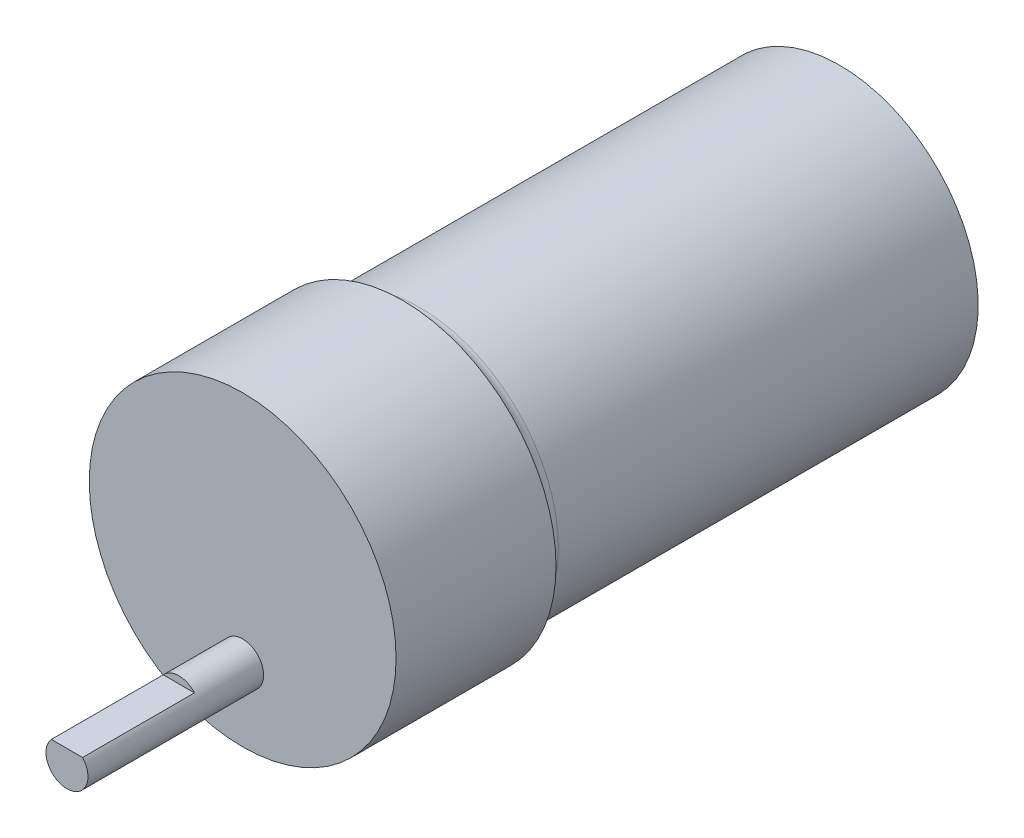
SolidWorks part; units mm, degrees
ref_plane "Front" through (0, 0, 0) normal (0, 0, 1) x (1, 0, 0)
ref_plane "Top" through (0, 0, 0) normal (0, 1, 0) x (1, 0, 0)
ref_plane "Right" through (0, 0, 0) normal (1, 0, 0) x (0, 0, -1)
sketch "Sketch2" plane through (0, 0, 0) normal (0, 0, 1) x (1, 0, 0)
  circle A0 centre (0, 0) radius 17.55
  dimension "D1" = 35.1
extrude "Boss-Extrude1" add sketch "Sketch2" along normal blind 68.3
sketch "Sketch3" plane through (0, 0, 0) normal (0, 0, -1) x (-1, 0, 0)
  circle A0 centre (0, 0) radius 15.85
  dimension "D1" = 31.7
sketch "Sketch4" plane through (0, 0, 0) normal (0, 0, -1) x (-1, 0, 0)
  circle A0 centre (0, 0) radius 15.85 construction
  circle A1 centre (0, 0) radius 17.55
  circle A2 centre (0, 0) radius 17.55
  circle A3 centre (0, 0) radius 15.85
  dimension "D1" = 0
extrude "Cut-Extrude1" cut sketch "Sketch4" against normal blind 50
sketch "Sketch5" plane through (0, 0, 68.3) normal (0, 0, 1) x (1, 0, 0)
  circle A0 centre (0, -9.25) radius 2.4
  dimension "D1" = 4.8
  dimension "D2" = 9.25
extrude "Boss-Extrude3" add sketch "Sketch5" along normal blind 20.1
sketch "Sketch6" plane through (0, 0, 88.4) normal (0, 0, 1) x (1, 0, 0)
  line L2 (-2.2835, -6.3582) -> (2.3187, -6.3582)
  line L3 (-2.2835, -6.3582) -> (-2.2835, -7.65)
  line L4 (-2.2835, -7.65) -> (2.3187, -7.65)
  line L5 (2.3187, -6.3582) -> (2.3187, -7.65)
extrude "Cut-Extrude2" cut sketch "Sketch6" against normal blind 12.8
fillet "Fillet1" radius 2 1 edges at (-15.85, 0, 50)
